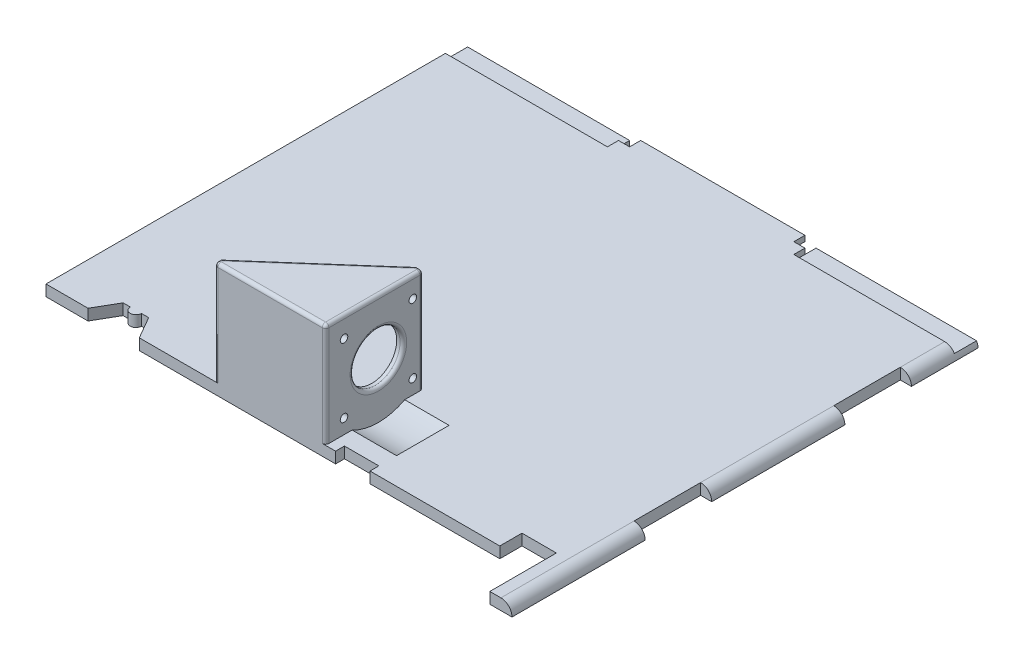
SolidWorks part; units mm, degrees
ref_plane "前基準面" through (0, 0, 0) normal (0, 0, 1) x (1, 0, 0)
ref_plane "上基準面" through (0, 0, 0) normal (0, 1, 0) x (1, 0, 0)
ref_plane "右基準面" through (0, 0, 0) normal (1, 0, 0) x (0, 0, -1)
sketch "草圖1" plane through (0, 0, 0) normal (0, 1, 0) x (1, 0, 0)
  line L0 (-36.2537, 43.5351) -> (203.7463, 43.5351)
  line L1 (203.7463, 43.5351) -> (203.7463, -286.4649)
  line L2 (198.7463, -286.4649) -> (198.7463, -256.4649)
  line L3 (198.7463, -256.4649) -> (183.2463, -256.4649)
  line L4 (183.2463, -256.4649) -> (183.2463, -266.4649)
  line L5 (183.2463, -266.4649) -> (124.7463, -266.4649)
  line L6 (124.7463, -266.4649) -> (124.7463, -262.4649)
  line L7 (124.7463, -262.4649) -> (109.2463, -262.4649)
  line L8 (109.2463, -262.4649) -> (109.2463, -266.4649)
  line L9 (109.2463, -266.4649) -> (-21.2537, -266.4649)
  line L10 (-21.2537, -266.4649) -> (-21.2537, 38.5351)
  line L11 (-21.2537, 38.5351) -> (-36.2537, 38.5351)
  line L12 (-36.2537, 38.5351) -> (-36.2537, 43.5351)
  line L13 (198.7463, -286.4649) -> (203.7463, -286.4649)
  line L15 (203.7463, -286.4649) -> (208.7463, -286.4649)
  line L16 (203.7463, -286.4649) -> (203.7463, -226.4649)
  line L17 (203.7463, -226.4649) -> (208.7463, -226.4649)
  line L18 (208.7463, -286.4649) -> (208.7463, -226.4649)
  line L19 (-36.2537, 43.5351) -> (-6.2537, 43.5351)
  line L20 (-36.2537, 43.5351) -> (-36.2537, 48.5351)
  line L21 (-36.2537, 48.5351) -> (-6.2537, 48.5351)
  line L22 (-6.2537, 43.5351) -> (-6.2537, 48.5351)
  line L23 (203.7463, 43.5351) -> (173.7463, 43.5351)
  line L24 (203.7463, 43.5351) -> (203.7463, 48.5351)
  line L25 (203.7463, 48.5351) -> (173.7463, 48.5351)
  line L26 (173.7463, 43.5351) -> (173.7463, 48.5351)
  line L27 (203.7463, 43.5351) -> (208.7463, 43.5351)
  line L28 (203.7463, 43.5351) -> (203.7463, -16.4649)
  line L29 (203.7463, -16.4649) -> (208.7463, -16.4649)
  line L30 (208.7463, 43.5351) -> (208.7463, -16.4649)
  line L31 (83.7463, 43.5351) -> (98.7463, 43.5351)
  line L32 (83.7463, 43.5351) -> (83.7463, 48.5351)
  line L33 (83.7463, 48.5351) -> (98.7463, 48.5351)
  line L34 (98.7463, 43.5351) -> (98.7463, 48.5351)
  line L35 (83.7463, 43.5351) -> (68.7463, 43.5351)
  line L36 (83.7463, 43.5351) -> (83.7463, 48.5351)
  line L37 (83.7463, 48.5351) -> (68.7463, 48.5351)
  line L38 (68.7463, 43.5351) -> (68.7463, 48.5351)
  line L39 (203.7463, -46.4649) -> (208.7463, -46.4649)
  line L40 (203.7463, -46.4649) -> (203.7463, -106.4649)
  line L41 (203.7463, -106.4649) -> (208.7463, -106.4649)
  line L42 (208.7463, -46.4649) -> (208.7463, -106.4649)
  line L43 (203.7463, -136.4649) -> (208.7463, -136.4649)
  line L44 (203.7463, -136.4649) -> (203.7463, -196.4649)
  line L45 (203.7463, -196.4649) -> (208.7463, -196.4649)
  line L46 (208.7463, -136.4649) -> (208.7463, -196.4649)
  dimension "D3" = 5
  dimension "D1" = 240
  dimension "D2" = 330
  dimension "D4" = 15
  dimension "D5" = 130.5
  dimension "D6" = 4
  dimension "D7" = 4
  dimension "D8" = 15.5
  dimension "D9" = 58.5
  dimension "D10" = 10
  dimension "D11" = 15.5
  dimension "D12" = 30
  dimension "D13" = 5
  dimension "D14" = 60
  dimension "D15" = 5
  dimension "D16" = 5
  dimension "D17" = 30
  dimension "D18" = 5
  dimension "D19" = 30
  dimension "D20" = 60
  dimension "D21" = 5
  dimension "D22" = 5
  dimension "D23" = 15
  dimension "D24" = 5
  dimension "D25" = 15
  dimension "D26" = 60
  dimension "D27" = 5
  dimension "D28" = 30
  dimension "D29" = 60
  dimension "D30" = 5
  dimension "D31" = 30
  dimension "D32" = 30
extrude "填料-伸長1" add sketch "草圖1" along normal blind 5 contours L2 L13 L1 L0 L12 L11 L10 L9 L8 L7 L6 L5 L4 L3 | L15 L18 L17 L1 | L30 L27 L1 L29 | L26 L0 L24 L25 | L0 L22 L21 L20 | L32 L33 L34 L31 | L36 L37 L38 L35 | L46 L45 L44 L43 | L42 L41 L40 L39 region at (-21.2537, 0, -46.0351) region at (91.0303, 0, 111.0679) region at (188.7463, 0, -46.0351) region at (206.2463, 0, -13.5351) region at (206.2463, 0, 256.4649)
fillet "圓角1" radius 5 4 edges at (208.7463, 5, -13.5351) (208.7463, 5, 76.4649) (208.7463, 5, 166.4649) (208.7463, 5, 256.4649)
sketch "草圖2" plane through (0, 5, 0) normal (0, 1, 0) x (1, 0, 0)
  line L1 (-36.2537, 48.5351) -> (208.7463, 48.5351)
  line L2 (-36.2537, 48.5351) -> (-36.2537, -76.4649)
  line L3 (-36.2537, -76.4649) -> (208.7463, -76.4649)
  line L4 (208.7463, 48.5351) -> (208.7463, -76.4649)
  dimension "D1" = 125
extrude "除料-伸長1" cut sketch "草圖2" against normal blind 5
sketch "草圖3" plane through (0, 0, 76.4649) normal (0, 0, -1) x (-1, 0, 0)
  line L1 (-56.7463, 0) -> (-130.7463, 0)
  line L2 (-56.7463, 0) -> (-56.7463, 2.5)
  line L3 (-56.7463, 2.5) -> (-130.7463, 2.5)
  line L4 (-130.7463, 0) -> (-130.7463, 2.5)
  line L5 (-135.7463, 2.5) -> (-208.7463, 2.5)
  line L6 (-135.7463, 2.5) -> (-135.7463, 5)
  line L7 (-135.7463, 5) -> (-208.7463, 5)
  line L8 (-208.7463, 2.5) -> (-208.7463, 5)
  line L17 (21.2537, 5) -> (-203.7463, 5) construction
  line L27 (-51.7463, 2.5) -> (21.2537, 2.5)
  line L28 (-51.7463, 2.5) -> (-51.7463, 5)
  line L29 (-51.7463, 5) -> (21.2537, 5)
  line L30 (21.2537, 2.5) -> (21.2537, 5)
  point P9 (-135.7463, 3.75)
  dimension "D1" = 2.5
  dimension "D2" = 74
  dimension "D3" = 2.5
  dimension "D4" = 73
  dimension "D5" = 5
  dimension "D6" = 5
  dimension "D11" = 73
extrude "除料-伸長2" cut sketch "草圖3" against normal blind 10
sketch "草圖4" plane through (0, 0, 76.4649) normal (0, 0, -1) x (-1, 0, 0)
  line L1 (-135.7463, 5) -> (-130.7463, 5)
  line L2 (-135.7463, 5) -> (-135.7463, 0)
  line L3 (-135.7463, 0) -> (-130.7463, 0)
  line L4 (-130.7463, 5) -> (-130.7463, 0)
  line L5 (-56.7463, 0) -> (-51.7463, 0)
  line L6 (-56.7463, 0) -> (-56.7463, 5)
  line L7 (-56.7463, 5) -> (-51.7463, 5)
  line L8 (-51.7463, 0) -> (-51.7463, 5)
extrude "除料-伸長3" cut sketch "草圖4" against normal blind 5
sketch "草圖5" plane through (0, 0, 266.4649) normal (0, 0, 1) x (1, 0, 0)
  line L0 (109.2463, 5) -> (-21.2537, 5) construction
  line L1 (104.7463, 5) -> (54.7463, 5)
  line L2 (104.7463, 5) -> (104.7463, 51.65)
  line L3 (104.7463, 51.65) -> (54.7463, 51.65)
  line L4 (54.7463, 5) -> (54.7463, 51.65)
  line L5 (124.7463, 5) -> (124.7463, 0) construction
  dimension "D1" = 50
  dimension "D2" = 46.65
  dimension "D3" = 20
  dimension "D4" = 0
extrude "填料-伸長2" add sketch "草圖5" against normal blind 47 contours L2 L1 L4 L3
sketch "草圖6" plane through (54.7463, 0, 0) normal (-1, 0, 0) x (0, 0, 1)
  line L0 (219.4649, 51.65) -> (266.4649, 51.65) construction
  line L1 (222.2649, 49.05) -> (263.6649, 49.05)
  line L2 (222.2649, 49.05) -> (222.2649, 5)
  line L3 (222.2649, 5) -> (263.6649, 5)
  line L4 (263.6649, 49.05) -> (263.6649, 5)
  line L5 (219.4649, 5) -> (219.4649, 51.65) construction
  line L6 (266.4649, 5) -> (266.4649, 51.65) construction
  line L7 (266.4649, 5) -> (86.4649, 5) construction
  dimension "D1" = 2.6
  dimension "D2" = 2.8
  dimension "D3" = 2.8
  dimension "D4" = 0
extrude "除料-伸長4" cut sketch "草圖6" against normal blind 47 contours L2 L1 L4 L3
sketch "草圖7" plane through (101.7463, 0, 0) normal (-1, 0, 0) x (0, 0, 1)
  line L0 (263.6649, 49.05) -> (263.6649, 5) construction
  line L1 (222.2649, 49.05) -> (263.6649, 49.05) construction
  line L2 (222.2649, 49.05) -> (222.2649, 5) construction
  line L5 (263.6649, 49.05) -> (263.6649, 5) construction
  circle A0 centre (242.6649, 27.02) radius 11.25
  dimension "D1" = 41.4
  dimension "D4" = 22.5
  dimension "D2" = 21
  dimension "D3" = 22.03
extrude "除料-伸長5" cut sketch "草圖7" against normal through all
sketch "草圖8" plane through (0, 51.65, 0) normal (0, 1, 0) x (1, 0, 0)
  line L4 (54.7463, -263.6649) -> (101.7463, -222.4649)
  line L8 (104.7463, -219.4649) -> (54.7463, -219.4649) construction
  line L9 (54.7463, -263.6649) -> (54.7463, -219.4649)
  line L13 (104.7463, -219.4649) -> (54.7463, -219.4649)
  line L14 (101.7463, -222.4649) -> (104.7463, -222.4649)
  line L15 (104.7463, -219.4649) -> (104.7463, -266.4649) construction
  line L16 (104.7463, -222.4649) -> (104.7463, -219.4649)
  dimension "D2" = 3
extrude "除料-伸長6" cut sketch "草圖8" against normal blind 46.65
sketch "草圖10" plane through (101.7463, 0, 0) normal (-1, 0, 0) x (0, 0, 1)
  circle A0 centre (227.1649, 42.52) radius 1.7
  circle A1 centre (258.1649, 42.52) radius 1.7
  circle A2 centre (258.1649, 11.52) radius 1.7
  circle A3 centre (227.1649, 11.52) radius 1.7
  circle A4 centre (242.6649, 27.02) radius 11.25 construction
  dimension "D1" = 3.4
  dimension "D2" = 3.4
  dimension "D3" = 3.4
  dimension "D4" = 3.4
  dimension "D5" = 15.5
  dimension "D6" = 15.5
  dimension "D7" = 15.5
  dimension "D8" = 15.5
  dimension "D9" = 15.5
  dimension "D10" = 15.5
  dimension "D11" = 15.5
  dimension "D12" = 15.5
extrude "除料-伸長7" cut sketch "草圖10" against normal through all
sketch "草圖13" plane through (104.7463, 0, 0) normal (1, 0, 0) x (0, 0, -1)
  circle A0 centre (-242.6649, 27.02) radius 25
  dimension "D1" = 50
extrude "除料-伸長9" cut sketch "草圖13" along normal blind 20
fillet "圓角11" radius 1.497 9 edges at (104.7463, 51.65, 244.4649) (79.7463, 51.65, 266.4649) (54.7463, 51.65, 265.0649) (78.2463, 51.65, 243.0649) (103.2463, 51.65, 222.4649) (54.7463, 28.325, 266.4649) (104.7463, 28.325, 266.4649) (104.7463, 27.02, 231.4149) (104.7463, 28.325, 222.4649)
sketch "草圖14" plane through (0, 5, 0) normal (0, 1, 0) x (1, 0, 0)
  line L0 (109.2463, -262.4649) -> (109.2463, -266.4649) construction
  line L8 (56.2433, -266.4649) -> (-21.2537, -266.4649) construction
  line L9 (20.7933, -266.4649) -> (15.0198, -256.4649)
  line L10 (15.0198, -256.4649) -> (3.4728, -256.4649)
  line L11 (3.4728, -256.4649) -> (-2.3007, -266.4649)
  line L12 (-2.3007, -266.4649) -> (3.4728, -276.4649)
  line L13 (3.4728, -276.4649) -> (15.0198, -276.4649)
  line L14 (15.0198, -276.4649) -> (20.7933, -266.4649)
  circle A0 centre (9.2463, -266.4649) radius 10 construction
  point P10 (0, 0)
  dimension "D1" = 0
  dimension "D3" = 20
  dimension "D2" = 100
extrude "除料-伸長10" cut sketch "草圖14" against normal through all
sketch "草圖17" plane through (0, 5, 0) normal (0, 1, 0) x (1, 0, 0)
  line L0 (15.0198, -256.4649) -> (3.4728, -256.4649) construction
  circle A0 centre (9.2463, -256.4649) radius 2.5
extrude "填料-伸長3" add sketch "草圖17" against normal blind 5
equation "\"1.5.0000mm\"=10"
